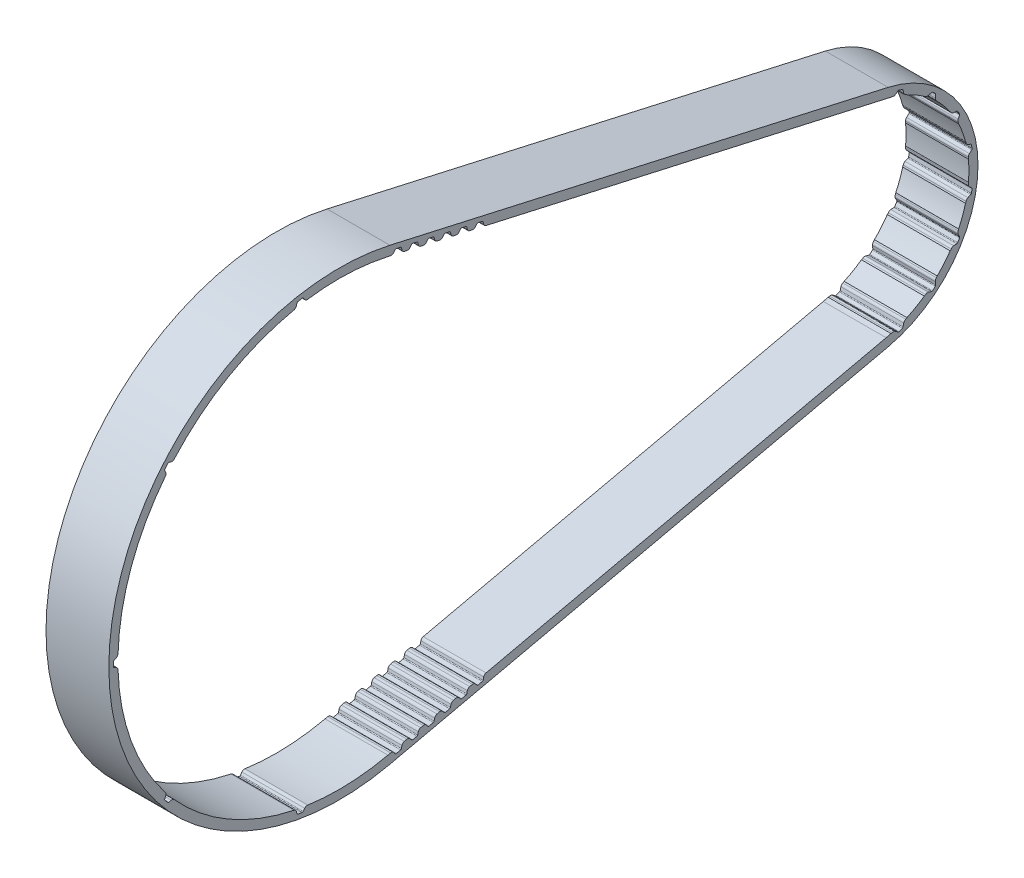
SolidWorks part; units mm, degrees
ref_plane "前视基准面" through (0, 0, 0) normal (0, 0, 1) x (1, 0, 0)
ref_plane "上视基准面" through (0, 0, 0) normal (0, 1, 0) x (1, 0, 0)
ref_plane "右视基准面" through (0, 0, 0) normal (1, 0, 0) x (0, 0, -1)
sketch "草图1" plane through (0, 0, 0) normal (1, 0, 0) x (0, 0, -1)
  line L0 (48.4, 214.61) -> (524.2, 107.305)
  line L1 (48.4, -214.61) -> (524.2, -107.305)
  line L2 (0, 0) -> (500, 0) construction
  line L3 (0, 0) -> (-363.6995, 0) construction
  line L4 (0, 0) -> (48.4, 214.61) construction
  arc A0 (48.4, 214.61) -> (48.4, -214.61) centre (0, 0) ccw
  arc A1 (524.2, -107.305) -> (524.2, 107.305) centre (500, 0) ccw
  dimension "d2" = 220
  dimension "d1" = 110
  dimension "dist" = 500
  dimension "Angle" = 102.709
sketch "草图2" plane through (0, 0, 0) normal (0, 0, 1) x (1, 0, 0)
  line L0 (-30, 220) -> (30, 220)
  line L1 (30, 220) -> (30, 211.3)
  line L2 (30, 211.3) -> (-30, 211.3)
  line L3 (-30, 211.3) -> (-30, 220)
  line L4 (0, 211.3) -> (0, 220) construction
  line L5 (0, -220) -> (0, 220) construction
  dimension "bs" = 60
  dimension "hs" = 8.7
sweep "扫描1" add profiles "草图2" path "草图1"
ref_axis "基准轴1" through (-33.0003, 0, 0) along (1, 0, 0)
ref_plane "基准面1" through (0, 0, -500) normal (0, 0, 1) x (1, 0, 0)
ref_axis "基准轴2" through (-33.0003, 0, -500) along (1, 0, 0)
sketch "草图3" plane through (30, 0, 0) normal (1, 0, 0) x (0, 0, -1)
  line L0 (0, 0) -> (-284.3079, 0) construction
  line L1 (-215.5495, -2.119) -> (-215.5495, 2.119)
  line L2 (-214.9925, 3.0155) -> (-212.8502, 4.0743)
  line L3 (-211.194, 6.7403) -> (-208.7736, 6.7403)
  line L4 (-208.7736, 6.7403) -> (-208.7736, -6.7403)
  line L5 (-211.194, -6.7403) -> (-208.7736, -6.7403)
  line L6 (-214.9925, -3.0155) -> (-212.8502, -4.0743)
  arc A0 (-214.9925, 3.0155) -> (-215.5495, 2.119) centre (-214.5495, 2.119) ccw
  arc A2 (-212.8502, 4.0743) -> (-211.194, 6.7403) centre (-214.1677, 6.7403) ccw
  arc A3 (46.486, 206.1231) -> (46.486, -206.1231) centre (0, 0) ccw construction
  arc A4 (-212.8502, -4.0743) -> (-211.194, -6.7403) centre (-214.1677, -6.7403) cw
  arc A5 (-214.9925, -3.0155) -> (-215.5495, -2.119) centre (-214.5495, -2.119) cw
  point P9 (-276.3079, 0)
  point P14 (-215.5495, 0)
  point P15 (-215.5495, 2.7403)
  point P23 (-208.7736, 0)
  point P24 (-279.9523, 0)
  dimension "ra" = 2.9738
  dimension "rr" = 1
  dimension "ht" = 4.3555
  dimension "D3" = 2.4204
  dimension "D4" = 4.3555
  dimension "Pb" = 13.4806
  dimension "PbS" = 5.4806
  dimension "angle" = 52.599
  dimension "S" = 8
extrude "切除-拉伸1" cut sketch "草图3" against normal through all
pattern_circular "阵列(圆周)1" count 9 over 360 about axis through (-33.0003, 0, 0) along (1, 0, 0) of "切除-拉伸1"
sketch "草图4" plane through (30, 0, 0) normal (1, 0, 0) x (0, 0, -1)
  line L0 (500, 0) -> (608.3289, 19.1013) construction
  line L1 (603.7482, 20.0607) -> (604.3526, 16.633)
  line L2 (600.9315, 10.9527) -> (599.9467, 10.779) construction
  line L3 (599.9467, 10.779) -> (597.6058, 24.0548)
  line L4 (604.0525, 15.7307) -> (601.8236, 13.6362)
  line L5 (603.1576, 20.8061) -> (600.3468, 22.0119)
  line L6 (598.5906, 24.2284) -> (597.6058, 24.0548) construction
  line L7 (599.9467, 10.779) -> (600.3329, 8.5885)
  line L8 (597.6058, 24.0548) -> (597.2195, 26.2453)
  line L9 (0, 0) -> (500, 0) construction
  line L10 (500, 0) -> (610, 0) construction
  arc A0 (601.8236, 13.6362) -> (600.9315, 10.9527) centre (603.86, 11.4691) ccw
  arc A2 (600.9315, 10.9527) -> (600.3329, 8.5885) centre (598.0029, 10.4363) cw
  arc A3 (604.0525, 15.7307) -> (604.3526, 16.633) centre (603.3678, 16.4594) ccw
  arc A4 (603.1576, 20.8061) -> (603.7482, 20.0607) centre (602.7634, 19.8871) cw
  arc A5 (600.3468, 22.0119) -> (598.5906, 24.2284) centre (601.5192, 24.7448) cw
  arc A6 (598.5906, 24.2284) -> (597.2195, 26.2453) centre (595.662, 23.7121) ccw
  point P0 (500, 0)
  point P15 (604.0504, 18.3469)
  point P17 (604.4464, 16.1008)
  point P25 (598.7762, 17.4169)
  dimension "D5" = 2.9738
  dimension "D6" = 1
  dimension "D8" = 2.9738
  dimension "D3" = 4.3555
  dimension "D4" = 1
  dimension "D7" = 4.3445
  dimension "D2" = 13.4806
  dimension "D1" = 3.4806
  dimension "D9" = 610
  dimension "D10" = 10
  dimension "D11" = 110
extrude "切除-拉伸2" cut sketch "草图4" against normal through all
pattern_circular "阵列(圆周)2" count 18 over 360 about axis through (-33.0003, 0, -500) along (1, 0, 0) of "切除-拉伸2"
sketch "草图11" plane through (0, 214.61, -48.4) normal (0, 0.9755, -0.22) x (1, 0, 0)
  line L1 (-30, 487.7499) -> (30, 487.7499)
  line L2 (-30, 487.7499) -> (-30, 0)
  line L3 (-30, 0) -> (30, 0)
  line L4 (30, 487.7499) -> (30, 0)
extrude "拉伸11" add sketch "草图11" against normal blind 8.7
mirror "镜向2" about plane through (0, 0, 0) normal (0, 1, 0) of "拉伸11"
sketch "草图5" plane through (30, 0, 0) normal (1, 0, 0) x (0, 0, -1)
  line L0 (0, 0) -> (47.4442, 210.3719) construction
  line L1 (47.4442, 210.3719) -> (56.5494, 208.3185) construction
  line L2 (56.5494, 208.3185) -> (9.1052, -2.0535) construction
  line L3 (9.1052, -2.0535) -> (0, 0) construction
  line L4 (54.4823, 208.7847) -> (58.6166, 207.8523)
  line L5 (59.3686, 207.1118) -> (59.9301, 204.7889)
  line L6 (62.023, 201.9509) -> (62.1664, 202.5868) construction
  line L7 (62.1664, 202.5868) -> (61.7264, 200.6358)
  line L8 (61.7264, 200.6358) -> (48.5761, 203.6015)
  line L9 (48.8727, 204.9166) -> (49.0161, 205.5525) construction
  line L10 (49.0161, 205.5525) -> (48.5761, 203.6015)
  line L11 (53.4853, 208.4386) -> (51.9811, 206.5816)
  line L12 (47.4442, 210.3719) -> (51.8442, 229.8819) construction
  arc A0 (59.9301, 204.7889) -> (62.1664, 202.5868) centre (62.8206, 205.4877) ccw
  arc A1 (59.3686, 207.1118) -> (58.6166, 207.8523) centre (58.3966, 206.8768) ccw
  arc A2 (53.4853, 208.4386) -> (54.4823, 208.7847) centre (54.2623, 207.8092) cw
  arc A3 (51.9811, 206.5816) -> (49.0161, 205.5525) centre (49.6703, 208.4534) cw
  point P2 (53.8763, 208.9213)
  point P13 (56.5494, 208.3185)
  point P14 (59.2226, 207.7156)
  point P23 (55.1512, 202.1187)
  dimension "D6" = 1
  dimension "D2" = 13.4806
  dimension "D4" = 4.3555
  dimension "D3" = 2.9738
  dimension "D1" = 5.4806
  dimension "D5" = 2
  dimension "D8" = 20
  dimension "D9" = 215.6555
  dimension "D22" = 9.3339
extrude "切除-拉伸3" cut sketch "草图5" against normal up to next
pattern_linear "阵列(线性)1" count 6 along (0, -0.22, -0.9755) of "切除-拉伸3"
mirror "镜向1" about plane through (0, 0, 0) normal (0, 1, 0) of "阵列(线性)1", "切除-拉伸3"
scale "缩放比例1" scale about centroid uniform scaling yes scale factor 0.1
scale "缩放比例2" scale about centroid uniform scaling yes scale factor 0.3
scale "缩放比例3" scale about centroid uniform scaling yes scale factor 10
scale "缩放比例4" scale about centroid uniform scaling yes scale factor 0.5
scale "缩放比例5" scale about centroid uniform scaling yes scale factor 1.3
equation "\"D1@基准面1\" = \"dist@草图1\""
equation "\"D3@草图4\" =\"D4@草图3\""
equation "\"D5@草图4\" =\"ra@草图3\""
equation "\"D6@草图4\" =\"rr@草图3\""
equation "\"D1@阵列(线性)1\" = \"RD1@注解\" / \"Pb@阵列(线性)1\"  "
equation "\"D3@草图5\" = \"ra@草图3\""
equation "\"D4@草图5\" = \"D4@草图3\""
equation "\"D6@草图5\" = \"rr@草图3\""
equation "\"D9@草图5\" =\"d2@草图1\" - \"hs@草图2\" + \"ht@草图3\""
equation "\"D1@草图5\" = \"PbS@草图3\""
equation "\"D4@草图3\" = \"ht@草图3\""
equation "\"D2@草图4\" = \"Pb@草图3\""
equation "\"D2@草图5\" = \"Pb@草图3\""
equation "\"PbS@草图3\" = \"Pb@草图3\" - \"S@草图3\""
equation "\"D7@草图4\" = \"hs@草图2\" - \"ht@草图3\""
equation "\"D8@草图4\" = \"D5@草图4\" "
equation "\"D9@草图4\" = \"dist@草图1\" + \"d1@草图1\""
equation "\"D1@拉伸11\" = \"hs@草图2\""
equation "\"D1@草图4\" = \"PbS@草图3\" - \"rr@草图3\" - \"rr@草图3\""
equation "\"D11@草图4\" = \"D9@草图4\" - \"dist@草图1\""
